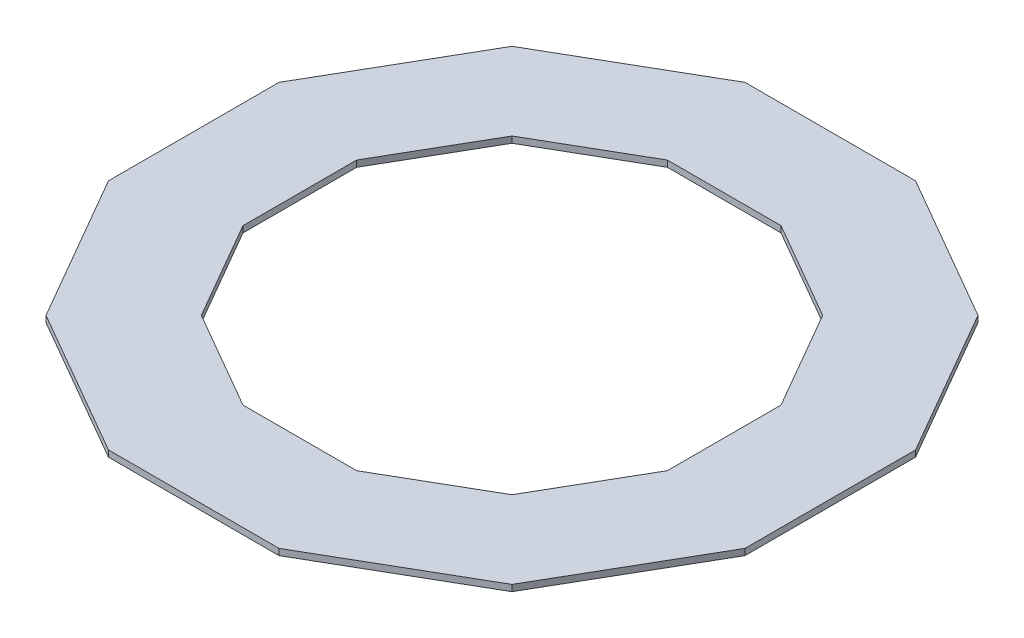
SolidWorks part; units mm, degrees
material "ABS PC"
ref_plane "Front Plane" through (0, 0, 0) normal (0, 0, 1) x (1, 0, 0)
ref_plane "Top Plane" through (0, 0, 0) normal (0, 1, 0) x (1, 0, 0)
ref_plane "Right Plane" through (0, 0, 0) normal (1, 0, 0) x (0, 0, -1)
sketch "Sketch1" plane through (0, 0, 0) normal (0, 1, 0) x (1, 0, 0)
  line L0 (39.444, 147.2071) -> (-39.444, 147.2071)
  line L1 (-39.444, 147.2071) -> (-107.7631, 107.7631)
  line L2 (-107.7631, 107.7631) -> (-147.2071, 39.444)
  line L3 (-147.2071, 39.444) -> (-147.2071, -39.444)
  line L4 (-147.2071, -39.444) -> (-107.7631, -107.7631)
  line L5 (-107.7631, -107.7631) -> (-39.444, -147.2071)
  line L6 (-39.444, -147.2071) -> (39.444, -147.2071)
  line L7 (39.444, -147.2071) -> (107.7631, -107.7631)
  line L8 (107.7631, -107.7631) -> (147.2071, -39.444)
  line L9 (147.2071, -39.444) -> (147.2071, 39.444)
  line L10 (147.2071, 39.444) -> (107.7631, 107.7631)
  line L11 (107.7631, 107.7631) -> (39.444, 147.2071)
  circle A0 centre (0, 0) radius 152.4
  dimension "D1" = 304.8
extrude "Boss-Extrude1" add sketch "Sketch1" against normal blind 2.921 contours L10 L11 L0 L1 L2 L3 L4 L5 L6 L7 L8 L9 region at (0, 0, 0)
sketch "Sketch3" plane through (0, 0, 0) normal (0, 1, 0) x (1, 0, 0)
  line L12 (-71.842, 71.842) -> (-26.296, 98.1381)
  line L13 (-26.296, 98.1381) -> (26.296, 98.1381)
  line L14 (26.296, 98.1381) -> (71.842, 71.842)
  line L15 (71.842, 71.842) -> (98.1381, 26.296)
  line L16 (98.1381, 26.296) -> (98.1381, -26.296)
  line L17 (98.1381, -26.296) -> (71.842, -71.842)
  line L18 (71.842, -71.842) -> (26.296, -98.1381)
  line L19 (26.296, -98.1381) -> (-26.296, -98.1381)
  line L20 (-26.296, -98.1381) -> (-71.842, -71.842)
  line L21 (-71.842, -71.842) -> (-98.1381, -26.296)
  line L22 (-98.1381, -26.296) -> (-98.1381, 26.296)
  line L23 (-98.1381, 26.296) -> (-71.842, 71.842)
  line L24 (-107.7631, 107.7631) -> (-147.2071, 39.444) construction
  line L25 (-39.444, 147.2071) -> (-107.7631, 107.7631) construction
  line L26 (39.444, 147.2071) -> (-39.444, 147.2071) construction
  line L27 (107.7631, 107.7631) -> (39.444, 147.2071) construction
  line L28 (147.2071, 39.444) -> (107.7631, 107.7631) construction
  line L29 (147.2071, -39.444) -> (147.2071, 39.444) construction
  line L30 (107.7631, -107.7631) -> (147.2071, -39.444) construction
  line L31 (39.444, -147.2071) -> (107.7631, -107.7631) construction
  line L32 (-39.444, -147.2071) -> (39.444, -147.2071) construction
  line L33 (-107.7631, -107.7631) -> (-39.444, -147.2071) construction
  line L34 (-147.2071, -39.444) -> (-107.7631, -107.7631) construction
  line L35 (-147.2071, 39.444) -> (-147.2071, -39.444) construction
  line L36 (-39.444, 147.2071) -> (39.444, -147.2071) construction
  line L37 (39.444, 147.2071) -> (-39.444, -147.2071) construction
  circle A0 centre (0, 0) radius 101.6
  dimension "D1" = 203.2
extrude "Cut-Extrude1" cut sketch "Sketch3" against normal through all contours L23 L22 L21 L20 L19 L18 L17 L16 L15 L14 L13 L12 region at (0, 0, 0)
